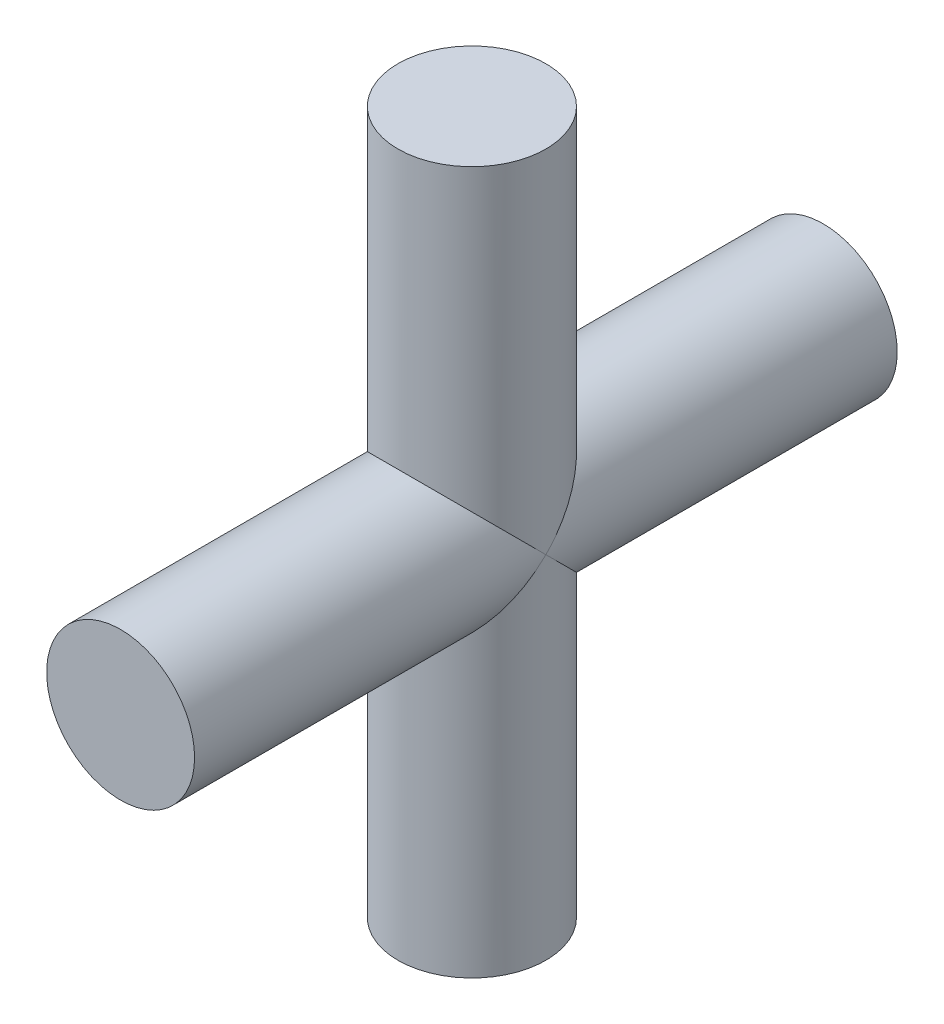
SolidWorks part; units mm, degrees
ref_plane "Front Plane" through (0, 0, 0) normal (0, 0, 1) x (1, 0, 0)
ref_plane "Top Plane" through (0, 0, 0) normal (0, 1, 0) x (1, 0, 0)
ref_plane "Right Plane" through (0, 0, 0) normal (1, 0, 0) x (0, 0, -1)
sketch "Sketch1" plane through (0, 0, 0) normal (0, 1, 0) x (1, 0, 0)
  circle A0 centre (0, 0) radius 2
  dimension "D1" = 4
extrude "Boss-Extrude1" add sketch "Sketch1" along normal blind 19
sketch "Sketch2" plane through (0, 0, 0) normal (0, 0, 1) x (1, 0, 0)
  line L0 (-2, 0) -> (2, 0) construction
  circle A0 centre (0, 9.5) radius 2
  dimension "D1" = 4
  dimension "D2" = 9.5
extrude "Boss-Extrude2" add sketch "Sketch2" along normal blind 9.5 and the other way blind 9.5
